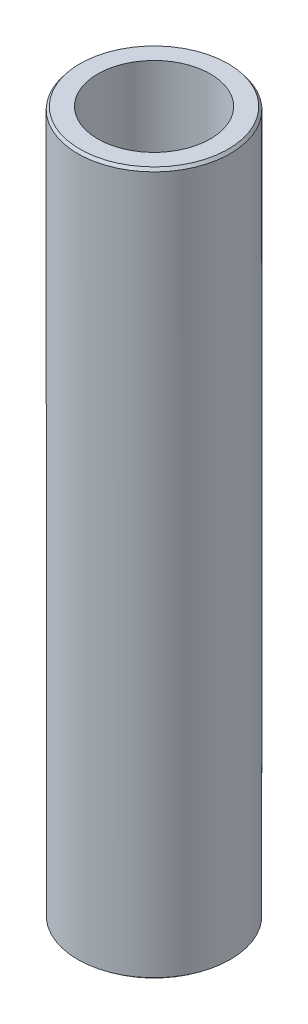
SolidWorks part; units mm, degrees
ref_plane "Front Plane" through (0, 0, 0) normal (0, 0, 1) x (1, 0, 0)
ref_plane "Top Plane" through (0, 0, 0) normal (0, 1, 0) x (1, 0, 0)
ref_plane "Right Plane" through (0, 0, 0) normal (1, 0, 0) x (0, 0, -1)
sketch "Sketch1" plane through (0, 0, 0) normal (0, 1, 0) x (1, 0, 0)
  circle A0 centre (0, 0) radius 50
  dimension "SHAFT_OD" = 100
extrude "Boss-Extrude1" add sketch "Sketch1" along normal blind 460.709
sketch "Sketch2" plane through (0, 0, 0) normal (0, 1, 0) x (1, 0, 0)
  circle A0 centre (0, 0) radius 36.9209
  dimension "BORE_D" = 73.8417
extrude "Cut-Extrude1" cut sketch "Sketch2" along normal through all
chamfer "Chamfer1" distance 1.8257 angle 38.251 2 edges at (0, 460.709, 50) (0, 0, 50) first distance on face at (0, 460.709, 50) first distance on face at (0, 0, 36.9209)
